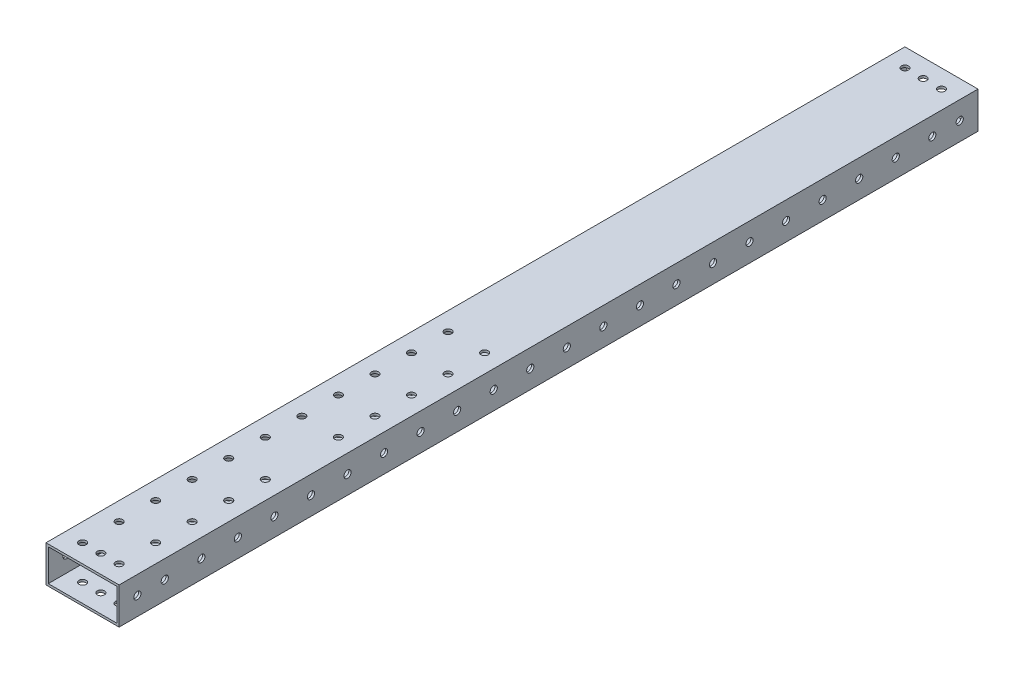
SolidWorks part; units mm, degrees
material "6061-T6 (SS)"
ref_plane "Front Plane" through (0, 0, 0) normal (0, 0, 1) x (1, 0, 0)
ref_plane "Top Plane" through (0, 0, 0) normal (0, 1, 0) x (1, 0, 0)
ref_plane "Right Plane" through (0, 0, 0) normal (1, 0, 0) x (0, 0, -1)
sketch "Sketch1" plane through (0, 0, 0) normal (0, 0, 1) x (1, 0, 0)
  line L1 (0, 0) -> (50.8, 0)
  line L2 (0, 0) -> (0, 25.4)
  line L3 (0, 25.4) -> (50.8, 25.4)
  line L4 (50.8, 0) -> (50.8, 25.4)
  dimension "D1" = 50.8
  dimension "D2" = 25.4
extrude "Boss-Extrude1" add sketch "Sketch1" along normal mid plane 596.9
shell "Shell1" thickness 1.5875 removed face at (25.4, 12.7, -298.45) removed face at (25.4, 12.7, 298.45)
sketch "Sketch2" plane through (0, 25.4, 0) normal (0, 1, 0) x (1, 0, 0)
  line L0 (50.8, -298.45) -> (50.8, 298.45) construction
  line L1 (50.8, -298.45) -> (0, -298.45) construction
  circle A0 centre (38.1, -285.75) radius 2.4892
  circle A1 centre (25.4, -285.75) radius 2.4892
  circle A2 centre (12.7, -285.75) radius 2.4892
  dimension "D1" = 4.9784
  dimension "D2" = 12.7
  dimension "D3" = 12.7
  dimension "D4" = 12.7
  dimension "D5" = 12.7
extrude "Cut-Extrude1" cut sketch "Sketch2" against normal through all
sketch "Sketch3" plane through (50.8, 0, 0) normal (1, 0, 0) x (0, 0, -1)
  line L0 (-298.45, 25.4) -> (298.45, 25.4) construction
  line L1 (-298.45, 0) -> (-298.45, 25.4) construction
  circle A0 centre (-285.75, 12.7) radius 2.4892
  dimension "D1" = 4.9784
  dimension "D2" = 12.7
  dimension "D3" = 12.7
extrude "Cut-Extrude2" cut sketch "Sketch3" against normal through all
mirror "Mirror1" about plane through (0, 0, 0) normal (0, 0, 1) of "Cut-Extrude1", "Cut-Extrude2"
sketch "Sketch4" plane through (50.8, 0, 0) normal (1, 0, 0) x (0, 0, -1)
  line L0 (-285.75, 12.7) -> (-266.7, 12.7) construction
  line L1 (-298.45, 0) -> (298.45, 0) construction
  line L2 (-298.45, 0) -> (-298.45, 25.4) construction
  circle A0 centre (-266.7, 12.7) radius 2.4892
  dimension "D1" = 4.9784
  dimension "D2" = 31.75
extrude "Cut-Extrude3" cut sketch "Sketch4" against normal through all and the other way through all
pattern_linear "LPattern1" count 22 spacing 25.4 along (0, 0, -1) of "Cut-Extrude3"
sketch "Sketch5" plane through (0, 0, 0) normal (0, -1, 0) x (1, 0, 0)
  circle A0 centre (12.7, 158.75) radius 2.4892 construction
  circle A1 centre (12.7, 184.15) radius 2.4892 construction
  circle A2 centre (38.1, 184.15) radius 2.4892 construction
  circle A3 centre (38.1, 209.55) radius 2.4892 construction
  circle A4 centre (12.7, 209.55) radius 2.4892 construction
  circle A5 centre (12.7, 234.95) radius 2.4892 construction
  circle A6 centre (38.1, 234.95) radius 2.4892 construction
  circle A7 centre (38.1, 260.35) radius 2.4892 construction
  circle A8 centre (12.7, 260.35) radius 2.4892 construction
  circle A9 centre (12.7, 158.75) radius 2.4892
  circle A10 centre (12.7, 184.15) radius 2.4892
  circle A11 centre (38.1, 184.15) radius 2.4892
  circle A12 centre (38.1, 209.55) radius 2.4892
  circle A13 centre (12.7, 209.55) radius 2.4892
  circle A14 centre (12.7, 234.95) radius 2.4892
  circle A15 centre (38.1, 234.95) radius 2.4892
  circle A16 centre (38.1, 260.35) radius 2.4892
  circle A17 centre (12.7, 260.35) radius 2.4892
  circle A18 centre (12.7, 31.75) radius 2.4892 construction
  circle A19 centre (38.1, 31.75) radius 2.4892 construction
  circle A20 centre (12.7, 57.15) radius 2.4892 construction
  circle A21 centre (38.1, 57.15) radius 2.4892 construction
  circle A22 centre (12.7, 82.55) radius 2.4892 construction
  circle A23 centre (38.1, 82.55) radius 2.4892 construction
  circle A24 centre (38.1, 107.95) radius 2.4892 construction
  circle A25 centre (38.1, 133.35) radius 2.4892 construction
  circle A26 centre (12.7, 107.95) radius 2.4892 construction
  circle A27 centre (12.7, 133.35) radius 2.4892 construction
  circle A28 centre (12.7, 31.75) radius 2.4892
  circle A29 centre (38.1, 31.75) radius 2.4892
  circle A30 centre (12.7, 57.15) radius 2.4892
  circle A31 centre (38.1, 57.15) radius 2.4892
  circle A32 centre (12.7, 82.55) radius 2.4892
  circle A33 centre (38.1, 82.55) radius 2.4892
  circle A34 centre (38.1, 107.95) radius 2.4892
  circle A35 centre (38.1, 133.35) radius 2.4892
  circle A36 centre (12.7, 107.95) radius 2.4892
  circle A37 centre (12.7, 133.35) radius 2.4892
extrude "Cut-Extrude4" cut sketch "Sketch5" against normal through all
